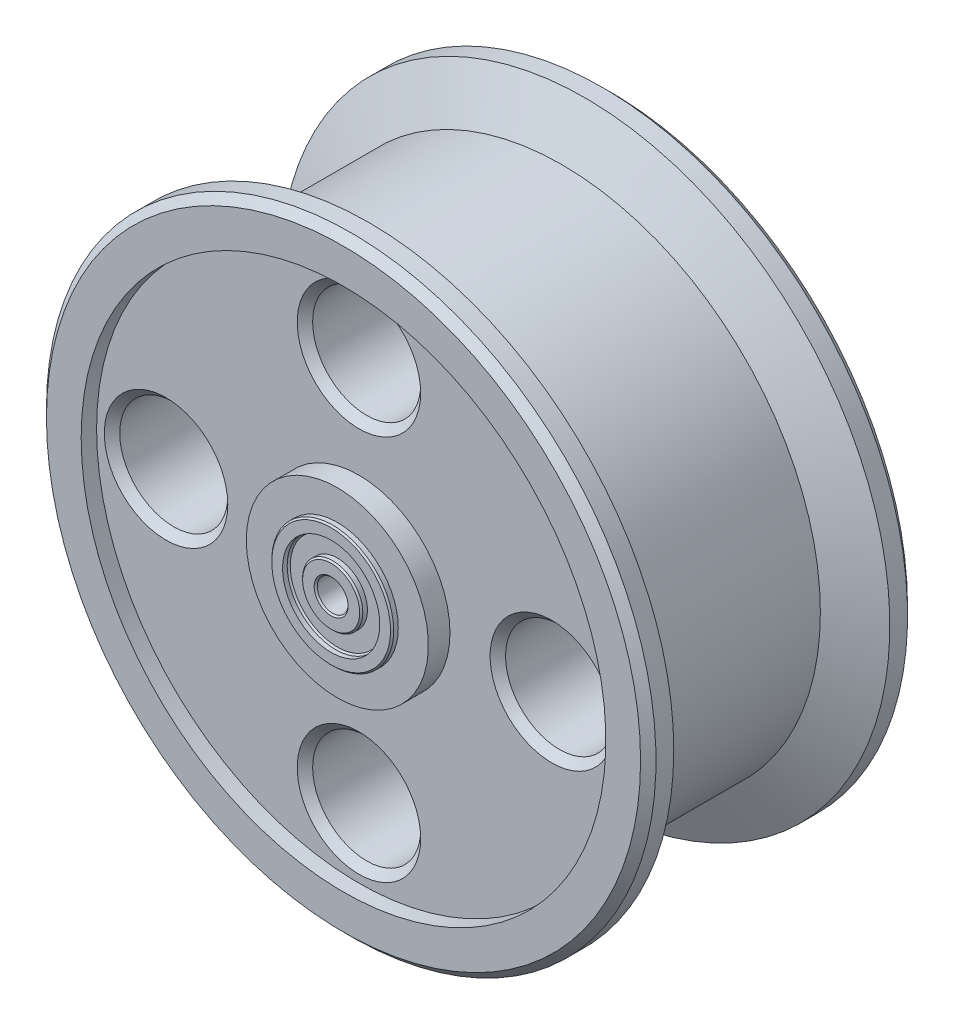
SolidWorks part; units mm, degrees
ref_plane "Front Plane" through (0, 0, 0) normal (0, 0, 1) x (1, 0, 0)
ref_plane "Top Plane" through (0, 0, 0) normal (0, 1, 0) x (1, 0, 0)
ref_plane "Right Plane" through (0, 0, 0) normal (1, 0, 0) x (0, 0, -1)
sketch "Sketch2" plane through (0, 0, 0) normal (0, 0, 1) x (1, 0, 0)
  circle A0 centre (0, 0) radius 50.165
extrude "Boss-Extrude1" add sketch "Sketch2" along normal blind 38.862
ref_plane "Plane1" through (0, 0, 0) normal (0, 0, -1) x (-1, 0, 0)
ref_plane "Plane2" through (0, 0, 38.862) normal (0, 0, 1) x (1, 0, 0)
sketch "Sketch3" plane through (0, 0, 0) normal (0, 0, -1) x (-1, 0, 0)
  circle A0 centre (0, 0) radius 14.986
extrude "Boss-Extrude2" add sketch "Sketch3" along normal blind 3.556
ref_plane "Plane3" through (0, 0, 19.431) normal (0, 0, -1) x (-1, 0, 0)
sketch "Sketch4" plane through (0, 0, 0) normal (0, 0, -1) x (-1, 0, 0)
  circle A0 centre (0, 0) radius 43.18
  circle A1 centre (0, 0) radius 50.165
extrude "Boss-Extrude3" add sketch "Sketch4" along normal blind 2.54
sketch "Sketch5" plane through (0, 0, 0) normal (0, 0, -1) x (-1, 0, 0)
  line L0 (0, 0) -> (31.75, 0) construction
  circle A0 centre (31.75, 0) radius 8.89
extrude "Cut-Extrude1" cut sketch "Sketch5" against normal through all
ref_axis "Axis1" through (0, 0, 38.862) along (0, 0, -1)
pattern_circular "CirPattern1" count 4 over 360 about axis through (0, 0, 38.862) along (0, 0, -1) of "Cut-Extrude1"
mirror "Mirror1" about plane through (0, 0, 19.431) normal (0, 0, -1) of "Boss-Extrude3"
mirror "Mirror2" about plane through (0, 0, 19.431) normal (0, 0, -1) of "Boss-Extrude2"
sketch "Sketch6" plane through (0, 0, 0) normal (0, 0, 1) x (1, 0, 0)
  circle A0 centre (0, 0) radius 2.54
extrude "Cut-Extrude2" cut sketch "Sketch6" along normal through all both and the other way through all
sketch "Sketch7" plane through (0, 0, -3.556) normal (0, 0, -1) x (-1, 0, 0)
  circle A0 centre (0, 0) radius 10.033
  circle A1 centre (0, 0) radius 8.001
extrude "Boss-Extrude4" add sketch "Sketch7" along normal blind 1.016
sketch "Sketch8" plane through (0, 0, -3.556) normal (0, 0, -1) x (-1, 0, 0)
  circle A0 centre (0, 0) radius 4.953
  circle A1 centre (0, 0) radius 2.54
extrude "Boss-Extrude5" add sketch "Sketch8" along normal blind 1.016
chamfer "Chamfer1" distance 0.254 angle 45 2 edges at (-8.001, 0, -4.572) (-10.033, 0, -3.556)
fillet "Fillet1" radius 0.254 2 edges at (-2.54, 0, -4.572) (-4.953, 0, -4.572)
chamfer "Chamfer2" distance 1.27 angle 45 8 edges at (0, -40.64, 0) (0, -40.64, 38.862) (-40.64, 0, 0) (-40.64, 0, 38.862) (0, 40.64, 0) (0, 40.64, 38.862) (40.64, 0, 0) (40.64, 0, 38.862)
chamfer "Chamfer3" distance 1.27 angle 45 2 edges at (-50.165, 0, -2.54) (-50.165, 0, 41.402)
sketch "Sketch9" plane through (0, 0, 0) normal (1, 0, 0) x (0, 0, -1)
  line L0 (-19.431, 50.165) -> (-19.431, -50.165) construction
  line L1 (1.27, 50.165) -> (-40.132, 50.165) construction
  line L2 (-40.132, -50.165) -> (1.27, -50.165) construction
  line L3 (-19.431, 50.165) -> (-19.431, 42.545) construction
  line L4 (-5.461, 42.545) -> (-33.401, 42.545)
  line L5 (-1.651, 50.165) -> (-37.211, 50.165)
  line L6 (-37.211, 50.165) -> (-33.401, 42.545)
  line L7 (-1.651, 50.165) -> (-5.461, 42.545)
revolve "Cut-Revolve1" cut sketch "Sketch9" angle 360 about axis through (0, 0, 38.862) along (0, 0, -1)
mirror "Mirror3" about plane through (0, 0, 19.431) normal (0, 0, -1) of "Boss-Extrude5"
mirror "Mirror4" about plane through (0, 0, 19.431) normal (0, 0, -1) of "Boss-Extrude4"
chamfer "Chamfer4" distance 0.254 angle 45 4 edges at (-8.001, 0, 42.418) (-2.54, 0, 43.434) (-4.953, 0, 43.434) (-10.033, 0, 43.434)
